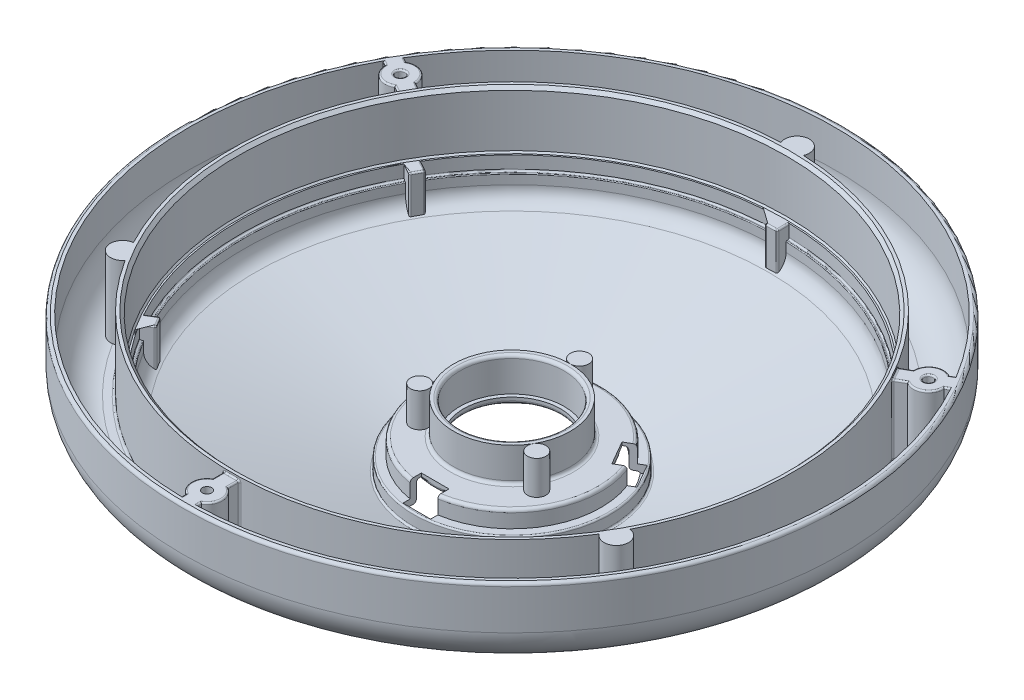
SolidWorks part; units mm, degrees
ref_plane "Front Plane" through (0, 0, 0) normal (0, 0, 1) x (1, 0, 0)
ref_plane "Top Plane" through (0, 0, 0) normal (0, 1, 0) x (1, 0, 0)
ref_plane "Right Plane" through (0, 0, 0) normal (1, 0, 0) x (0, 0, -1)
sketch "Sketch1" plane through (0, 0, 0) normal (0, 0, 1) x (1, 0, 0)
  line L0 (-106.265, 46.5) -> (-105.265, 46.5)
  line L1 (-105.265, 46.5) -> (-105.265, 34.5)
  line L2 (-94.265, 23.5) -> (-92.015, 23.5)
  line L3 (-91.265, 24.25) -> (-91.265, 47.5)
  line L4 (-91.265, 47.5) -> (-90.265, 47.5)
  line L5 (-89.265, 46.5) -> (-89.265, 29.5)
  line L6 (-88.765, 29) -> (-88.265, 29)
  line L7 (-88.265, 29) -> (-88.265, 25)
  line L8 (-87.765, 24.5) -> (-87.515, 24.5)
  line L9 (-87.265, 24.25) -> (-87.265, 21.2906)
  line L11 (-32, 2.6595) -> (-32, 6)
  line L12 (-31.5, 6.5) -> (-29, 6.5)
  line L13 (-29, 6.5) -> (-29, 11)
  line L14 (-28, 12) -> (-20, 12)
  line L15 (-19, 13) -> (-19, 23)
  line L16 (-19, 23) -> (-18, 23)
  line L17 (-17, 22) -> (-17, 12)
  line L18 (-17, 12) -> (-15.75, 12)
  line L19 (-15.75, 12) -> (-15.75, 11)
  line L21 (-27, 10) -> (-27, 5.5)
  line L22 (-28, 4.5) -> (-28.8583, 4.5)
  line L23 (-107.265, 45.5) -> (-107.265, 32.5)
  line L24 (-96.265, 21.5) -> (-91.765, 21.5)
  line L25 (-29.8583, 3.5) -> (-29.8583, 0.6318)
  line L26 (-32.635, 2.1781) -> (-83.6152, 16.4764)
  line L28 (-26, 11) -> (-25.5, 11)
  line L29 (-16.75, 10) -> (-24.75, 10)
  line L30 (-25, 10.25) -> (-25, 10.5)
  line L31 (-91.265, 21) -> (-91.265, 18.4569)
  line L34 (-91.265, 14.5) -> (-29.8583, 0) construction
  line L35 (-87.265, 17.5) -> (-32, 2)
  line L36 (-87.4141, 13.5907) -> (-30.4732, 0.1452)
  line L37 (0, 0) -> (0, 67.3301) construction
  line L38 (-90.265, 47.5) -> (-89.265, 46.5)
  line L39 (-89.265, 29.5) -> (-88.765, 29)
  arc A0 (-28.8583, 4.5) -> (-29.8583, 3.5) centre (-28.8583, 3.5) ccw
  arc A1 (-27, 5.5) -> (-28, 4.5) centre (-28, 5.5) cw
  arc A2 (-26, 11) -> (-27, 10) centre (-26, 10) ccw
  arc A3 (-15.75, 11) -> (-16.75, 10) centre (-16.75, 11) cw
  arc A4 (-18, 23) -> (-17, 22) centre (-18, 22) cw
  arc A5 (-29, 11) -> (-28, 12) centre (-28, 11) cw
  arc A6 (-106.265, 46.5) -> (-107.265, 45.5) centre (-106.265, 45.5) ccw
  arc A7 (-25.5, 11) -> (-25, 10.5) centre (-25.5, 10.5) cw
  arc A8 (-24.75, 10) -> (-25, 10.25) centre (-24.75, 10.25) cw
  arc A9 (-20, 12) -> (-19, 13) centre (-20, 13) ccw
  arc A10 (-32, 6) -> (-31.5, 6.5) centre (-31.5, 6) cw
  arc A11 (-92.015, 23.5) -> (-91.265, 24.25) centre (-92.015, 24.25) ccw
  arc A12 (-88.265, 25) -> (-87.765, 24.5) centre (-87.765, 25) ccw
  arc A13 (-87.515, 24.5) -> (-87.265, 24.25) centre (-87.515, 24.25) cw
  arc A14 (-32, 2.6595) -> (-32.635, 2.1781) centre (-32.5, 2.6595) cw
  arc A15 (-29.8583, 0.6318) -> (-30.4732, 0.1452) centre (-30.3583, 0.6318) cw
  arc A16 (-87.265, 21.2906) -> (-83.6152, 16.4764) centre (-82.265, 21.2906) ccw
  arc A17 (-91.265, 18.4569) -> (-87.4141, 13.5907) centre (-86.265, 18.4569) ccw
  arc A18 (-107.265, 32.5) -> (-96.265, 21.5) centre (-96.265, 32.5) ccw
  arc A19 (-105.265, 34.5) -> (-94.265, 23.5) centre (-94.265, 34.5) ccw
  arc A20 (-91.765, 21.5) -> (-91.265, 21) centre (-91.765, 21) cw
  point P2 (-93.14, 23.5)
  point P6 (-89.265, 47.5)
  point P7 (-89.265, 29)
  point P31 (-28.4291, 4.5)
  point P39 (-27, 4.5)
  point P42 (-27, 11)
  point P45 (-15.75, 10)
  point P48 (-17, 23)
  point P53 (-107.265, 46.5)
  point P56 (-25, 11)
  point P59 (-25, 10)
  point P62 (-19, 12)
  point P65 (-32, 6.5)
  point P70 (-91.265, 23.5)
  point P75 (-88.265, 24.5)
  point P78 (-87.265, 24.5)
  point P93 (-107.265, 21.5)
  point P98 (-91.265, 21.5)
  dimension "D28" = 4
  dimension "D33" = 1
  dimension "D34" = 0.5
  dimension "D35" = 0.25
  dimension "D36" = 1
  dimension "D39" = 0.5
  dimension "D40" = 0.75
  dimension "D41" = 0.5
  dimension "D43" = 0.25
  dimension "D45" = 0.5
  dimension "D46" = 5
  dimension "D47" = 11
  dimension "D48" = 0.5
  dimension "D1" = 14
  dimension "D2" = 2
  dimension "D3" = 2
  dimension "D4" = 2
  dimension "D5" = 107.265
  dimension "D6" = 46.5
  dimension "D7" = 25
  dimension "D8" = 18.5
  dimension "D9" = 1
  dimension "D10" = 1
  dimension "D11" = 4.5
  dimension "D12" = 7
  dimension "D13" = 32
  dimension "D14" = 7
  dimension "D15" = 2
  dimension "D16" = 2
  dimension "D17" = 6.5
  dimension "D18" = 2
  dimension "D19" = 0
  dimension "D20" = 12
  dimension "D21" = 11
  dimension "D22" = 2
  dimension "D23" = 4.5
  dimension "D24" = 15.75
  dimension "D25" = 11
  dimension "D26" = 17
  dimension "D27" = 29
  dimension "D29" = 2
  dimension "D30" = 9.25
  dimension "D31" = 2
  dimension "D32" = 3
  dimension "D37" = 2.381
  dimension "D38" = 24
revolve "Revolve1" add sketch "Sketch1" angle 360 about L37
sketch "Sketch2" plane through (0, 12, 0) normal (0, 1, 0) x (1, 0, 0)
  line L0 (0, 0) -> (0, 135.3376) construction
  line L1 (0, 0) -> (171.5153, -99.0244) construction
  line L2 (0, 0) -> (-123.0376, -71.0358) construction
  line L3 (0, 19) -> (0, 22) construction
  circle A0 centre (0, 0) radius 19 construction
  circle A1 centre (0, 0) radius 19 construction
  circle A2 centre (0, 22) radius 3
  circle A3 centre (19.0526, -11) radius 3
  circle A4 centre (-19.0526, -11) radius 3
  point P19 (0, 0)
  dimension "D4" = 3
  dimension "D1" = 120
  dimension "D2" = 120
  dimension "D3" = 3
extrude "Boss-Extrude3" add sketch "Sketch2" along normal blind 11 separate body
sketch "Sketch3" plane through (0, 23.5, 0) normal (0, 1, 0) x (1, 0, 0)
  line L0 (0, 0) -> (19.0526, -11) construction
  line L1 (19.0526, -11) -> (95.0819, -54.8956) construction
  line L2 (76.8727, -44.3825) -> (80.3368, -46.3825)
  circle A0 centre (0, 0) radius 88.765 construction
  circle A1 centre (0, 0) radius 88.765
  arc A2 (77.135, -48.78) -> (80.8123, -42.4109) centre (80.3368, -46.3825) ccw
  circle A3 centre (0, 0) radius 91.265 construction
  arc A4 (77.135, -48.78) -> (80.8123, -42.4109) centre (0, 0) ccw
  arc A5 (-80.8123, -42.4109) -> (-77.135, -48.78) centre (0, 0) ccw
  arc A6 (-80.8123, -42.4109) -> (-77.135, -48.78) centre (-80.3368, -46.3825) ccw
  arc A7 (3.6773, 91.1909) -> (-3.6773, 91.1909) centre (0, 0) ccw
  arc A8 (3.6773, 91.1909) -> (-3.6773, 91.1909) centre (0, 92.765) ccw
  point P23 (0, 0)
  dimension "D2" = 4
  dimension "D1" = 4
  dimension "D3" = 3
extrude "Boss-Extrude4" add sketch "Sketch3" along normal through all
sketch "Sketch6" plane through (0, 29, 0) normal (0, 1, 0) x (1, 0, 0)
  line L0 (0, 0) -> (19.0526, -11) construction
  line L1 (19.0526, -11) -> (112.9006, -65.1832) construction
  line L2 (76.4397, -44.1325) -> (74.7077, -43.1325) construction
  line L3 (71.9943, -43.9308) -> (75.506, -45.8459)
  line L4 (71.9943, -43.9308) -> (73.9093, -40.4191)
  line L5 (75.506, -45.8459) -> (77.4211, -42.3342)
  line L6 (73.9093, -40.4191) -> (77.4211, -42.3342)
  line L7 (71.9943, -43.9308) -> (77.4211, -42.3342) construction
  line L8 (75.506, -45.8459) -> (73.9093, -40.4191) construction
  line L9 (-2.0481, -84.3143) -> (-1.9507, -88.3131)
  line L10 (-2.0481, -84.3143) -> (1.9507, -84.2169)
  line L11 (1.9507, -84.2169) -> (2.0481, -88.2157)
  line L12 (-1.9507, -88.3131) -> (2.0481, -88.2157)
  line L13 (-74.0423, -40.3834) -> (-77.4567, -42.4672)
  line L14 (-74.0423, -40.3834) -> (-71.9586, -43.7978)
  line L15 (-71.9586, -43.7978) -> (-75.373, -45.8816)
  line L16 (-77.4567, -42.4672) -> (-75.373, -45.8816)
  line L17 (-71.9943, 43.9308) -> (-75.506, 45.8459)
  line L18 (-71.9943, 43.9308) -> (-73.9093, 40.4191)
  line L19 (-73.9093, 40.4191) -> (-77.4211, 42.3342)
  line L20 (-75.506, 45.8459) -> (-77.4211, 42.3342)
  line L21 (2.0481, 84.3143) -> (1.9507, 88.3131)
  line L22 (2.0481, 84.3143) -> (-1.9507, 84.2169)
  line L23 (-1.9507, 84.2169) -> (-2.0481, 88.2157)
  line L24 (1.9507, 88.3131) -> (-2.0481, 88.2157)
  line L25 (74.0423, 40.3834) -> (77.4567, 42.4672)
  line L26 (74.0423, 40.3834) -> (71.9586, 43.7978)
  line L27 (71.9586, 43.7978) -> (75.373, 45.8816)
  line L28 (77.4567, 42.4672) -> (75.373, 45.8816)
  circle A0 centre (0, 0) radius 88.265 construction
  point P36 (0, 0)
  dimension "D1" = 2
  dimension "D2" = 4
  dimension "D3" = 4
  dimension "D4" = 88.2394
  dimension "D5" = 6
extrude "Boss-Extrude6" add sketch "Sketch6" against normal up to next
fillet "Fillet1" radius 0.5 30 edges at (2.0003, 29, -86.2788) (2.0481, 22.8706, -84.3143) (0.0487, 29, -84.2656) (-1.9507, 22.8485, -84.2169) (-1.9994, 29, -86.2163) (75.7198, 29, -41.4071) (74.0423, 22.8706, -40.3834) (73.0005, 29, -42.0906) (71.9586, 22.8485, -43.7978) (73.6658, 29, -44.8397) (73.7195, 29, 44.8717) (71.9943, 22.8706, 43.9308) (73.9093, 22.8485, 40.4191) (75.6652, 29, 41.3766) (72.9518, 29, 42.175) (-2.0481, 22.8706, 84.3143) (-2.0003, 29, 86.2788) (-0.0487, 29, 84.2656) (1.9507, 22.8485, 84.2169) (1.9994, 29, 86.2163) (-74.0423, 22.8706, 40.3834) (-75.7198, 29, 41.4071) (-71.9586, 22.8485, 43.7978) (-73.0005, 29, 42.0906) (-73.6658, 29, 44.8397) (-73.7195, 29, -44.8717) (-75.6652, 29, -41.3766) (-71.9943, 22.8706, -43.9308) (-73.9093, 22.8485, -40.4191) (-72.9518, 29, -42.175)
sketch "Sketch8" plane through (0, 46.5, 0) normal (0, 1, 0) x (1, 0, 0)
  line L0 (0, 0) -> (19.0526, -11) construction
  line L1 (19.0526, -11) -> (114.5131, -66.1142) construction
  line L2 (0, 0) -> (0, -134.6557) construction
  line L3 (-2.5, -91.2308) -> (-2.5, -94.9349)
  line L4 (2.5, 0) -> (2.5, -1.4434)
  line L5 (0, -91.265) -> (0, -105.265) construction
  line L6 (2.5, -91.2308) -> (2.5, -94.9349)
  line L7 (2.5, -103.5951) -> (2.5, -105.2353)
  line L8 (2.5, 0) -> (2.5, -134.6557) construction
  line L9 (-2.5, 0) -> (-2.5, -134.6557) construction
  line L10 (-2.5, -103.5951) -> (-2.5, -105.2353)
  line L11 (-90.966, 49.6325) -> (-92.3865, 50.4526)
  line L12 (-88.466, 53.9626) -> (-89.8865, 54.7827)
  line L13 (-77.7581, 47.7804) -> (-80.966, 49.6325)
  line L14 (-80.2581, 43.4503) -> (-83.466, 45.3024)
  line L15 (88.466, 53.9626) -> (89.8865, 54.7827)
  line L16 (90.966, 49.6325) -> (92.3865, 50.4526)
  line L17 (80.2581, 43.4503) -> (83.466, 45.3024)
  line L18 (77.7581, 47.7804) -> (80.966, 49.6325)
  arc A0 (-77.135, -48.78) -> (77.135, -48.78) centre (0, 0) ccw construction
  arc A1 (-2.5, -91.2308) -> (2.5, -91.2308) centre (0, 0) ccw
  circle A2 centre (0, 0) radius 105.265 construction
  arc A3 (-2.5, -105.2353) -> (2.5, -105.2353) centre (0, 0) ccw
  arc A4 (2.5, -103.5951) -> (2.5, -94.9349) centre (0, -99.265) ccw
  circle A5 centre (0, -99.265) radius 1.5
  arc A6 (-2.5, -94.9349) -> (-2.5, -103.5951) centre (0, -99.265) ccw
  arc A7 (-89.8865, 54.7827) -> (-92.3865, 50.4526) centre (0, 0) ccw
  arc A8 (-80.966, 49.6325) -> (-88.466, 53.9626) centre (-85.966, 49.6325) ccw
  arc A9 (-77.7581, 47.7804) -> (-80.2581, 43.4503) centre (0, 0) ccw
  arc A10 (-90.966, 49.6325) -> (-83.466, 45.3024) centre (-85.966, 49.6325) ccw
  circle A11 centre (-85.966, 49.6325) radius 1.5
  arc A12 (92.3865, 50.4526) -> (89.8865, 54.7827) centre (0, 0) ccw
  arc A13 (83.466, 45.3024) -> (90.966, 49.6325) centre (85.966, 49.6325) ccw
  arc A14 (80.2581, 43.4503) -> (77.7581, 47.7804) centre (0, 0) ccw
  arc A15 (88.466, 53.9626) -> (80.966, 49.6325) centre (85.966, 49.6325) ccw
  circle A16 centre (85.966, 49.6325) radius 1.5
  point P51 (0, 0)
  circle M13 centre (0, 0) radius 105.265
  dimension "D2" = 2.5
  dimension "D4" = 10
  dimension "D5" = 3
  dimension "D1" = 60
  dimension "D6" = 6
  dimension "D3" = 2.5
  dimension "D7" = 3
extrude "Boss-Extrude7" add sketch "Sketch8" against normal up to next contours L3 A6 L10 L7 A4 L6 A1 A5 M13 | L15 A15 L18 A14 L17 A13 L16 A16 M13 | L11 A10 L14 A9 L13 A8 L12 A11 M13
fillet "Fillet2" radius 0.5 47 edges at (79.3825, 23.5, -48.7183) (2.5, 23.5, 93.1064) (-79.3825, 23.5, -48.7183) (77.9461, 23.7224, -47.889) (2.5, 24.7495, 92.5407) (-77.9461, 23.7224, -47.889) (77.7581, 35.375, -47.7804) (2.5, 35.375, 91.2308) (-77.7581, 35.375, -47.7804) (79.0378, 46.5, -45.6325) (0, 46.5, 91.265) (-79.0378, 46.5, -45.6325) (81.8825, 23.5, -44.3882) (80.4461, 23.7224, -43.5588) (-2.5, 23.5, 93.1064) (-2.5, 24.7495, 92.5407) (-81.8825, 23.5, -44.3882) (-80.4461, 23.7224, -43.5588) (80.2581, 35.375, -43.4503) (89.1762, 46.5, -54.3727) (79.3621, 46.5, -48.7065) (83.466, 46.5, -53.9626) (91.6762, 46.5, -50.0425) (81.8621, 46.5, -44.3763) (88.466, 46.5, -45.3024) (85.966, 46.5, -48.1325) (-85.966, 46.5, -48.1325) (-2.5, 35.375, 91.2308) (-2.5, 46.5, 104.4152) (-2.5, 46.5, 93.0828) (-5, 46.5, 99.265) (2.5, 46.5, 93.0828) (2.5, 46.5, 104.4152) (5, 46.5, 99.265) (-80.2581, 35.375, -43.4503) (-91.6762, 46.5, -50.0425) (-89.1762, 46.5, -54.3727) (-79.3621, 46.5, -48.7065) (-83.466, 46.5, -53.9626) (-81.8621, 46.5, -44.3763) (-88.466, 46.5, -45.3024)
sketch "Sketch9" plane through (0, 12, 0) normal (0, 1, 0) x (1, 0, 0)
  line L0 (0, 0) -> (19.0526, -11) construction
  line L1 (19.0526, -11) -> (137.0771, -79.1415) construction
  line L2 (0, 0) -> (111.6243, 64.4463) construction
  line L3 (19.4006, 16.3971) -> (24.5968, 19.3971)
  line L4 (19.4006, 16.3971) -> (23.9006, 8.6029)
  line L5 (24.5968, 19.3971) -> (29.0968, 11.6029)
  line L6 (23.9006, 8.6029) -> (29.0968, 11.6029)
  line L7 (19.4006, 16.3971) -> (29.0968, 11.6029) construction
  line L8 (24.5968, 19.3971) -> (23.9006, 8.6029) construction
  line L9 (4.5, -25) -> (4.5, -31)
  line L10 (4.5, -25) -> (-4.5, -25)
  line L11 (-4.5, -25) -> (-4.5, -31)
  line L12 (4.5, -31) -> (-4.5, -31)
  line L13 (-23.9006, 8.6029) -> (-29.0968, 11.6029)
  line L14 (-23.9006, 8.6029) -> (-19.4006, 16.3971)
  line L15 (-19.4006, 16.3971) -> (-24.5968, 19.3971)
  line L16 (-29.0968, 11.6029) -> (-24.5968, 19.3971)
  circle A0 centre (0, 0) radius 28 construction
  circle A1 centre (0, 0) radius 28
  point P9 (24.2487, 14)
  point P11 (24.2487, 14)
  point P26 (0, 0)
  circle M7 centre (0, 0) radius 28
  dimension "D1" = 60
  dimension "D2" = 9
  dimension "D3" = 6
  dimension "D4" = 0
  dimension "D5" = 3
extrude "Cut-Extrude1" cut sketch "Sketch9" against normal blind 8 contours L6 L5 L3 M7 | L4 L6 L3 M7 | L14 L15 L13 M7 | L16 L13 L15 M7 | L10 L11 L9 M7 | L12 L9 L11 M7
